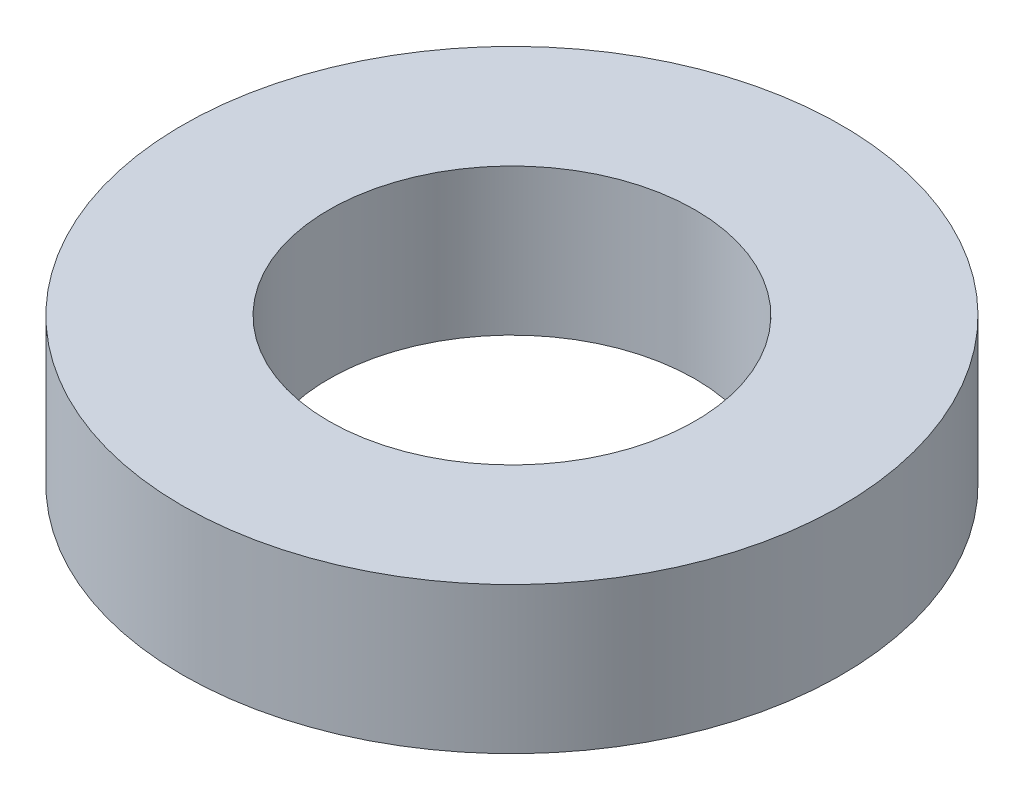
SolidWorks part; units mm, degrees
ref_plane "Front Plane" through (0, 0, 0) normal (0, 0, 1) x (1, 0, 0)
ref_plane "Top Plane" through (0, 0, 0) normal (0, 1, 0) x (1, 0, 0)
ref_plane "Right Plane" through (0, 0, 0) normal (1, 0, 0) x (0, 0, -1)
sketch "Sketch1" plane through (0, 0, 0) normal (0, 1, 0) x (1, 0, 0)
  circle A0 centre (0, 0) radius 67.5
  dimension "FLANGE_OD" = 135
extrude "Boss-Extrude1" add sketch "Sketch1" along normal blind 30
sketch "Sketch2" plane through (0, 0, 0) normal (0, 1, 0) x (1, 0, 0)
  circle A0 centre (0, 0) radius 37.5
  dimension "BORE_D" = 75
extrude "Cut-Extrude1" cut sketch "Sketch2" along normal through all
sketch "Sketch3" plane through (0, 30, 0) normal (0, 1, 0) x (1, 0, 0)
  circle A0 centre (0, 0) radius 23.9951 construction
  circle A1 centre (-23.9951, 0) radius 2.999
  dimension "BOLT_D" = 5.9979
  dimension "BOLT_PCD" = 47.9902
extrude "Cut-Extrude2" cut sketch "Sketch3" against normal blind 29.2897 rebuild error yes
pattern_circular "CirPattern1" count 4 over 360 rebuild error yes
